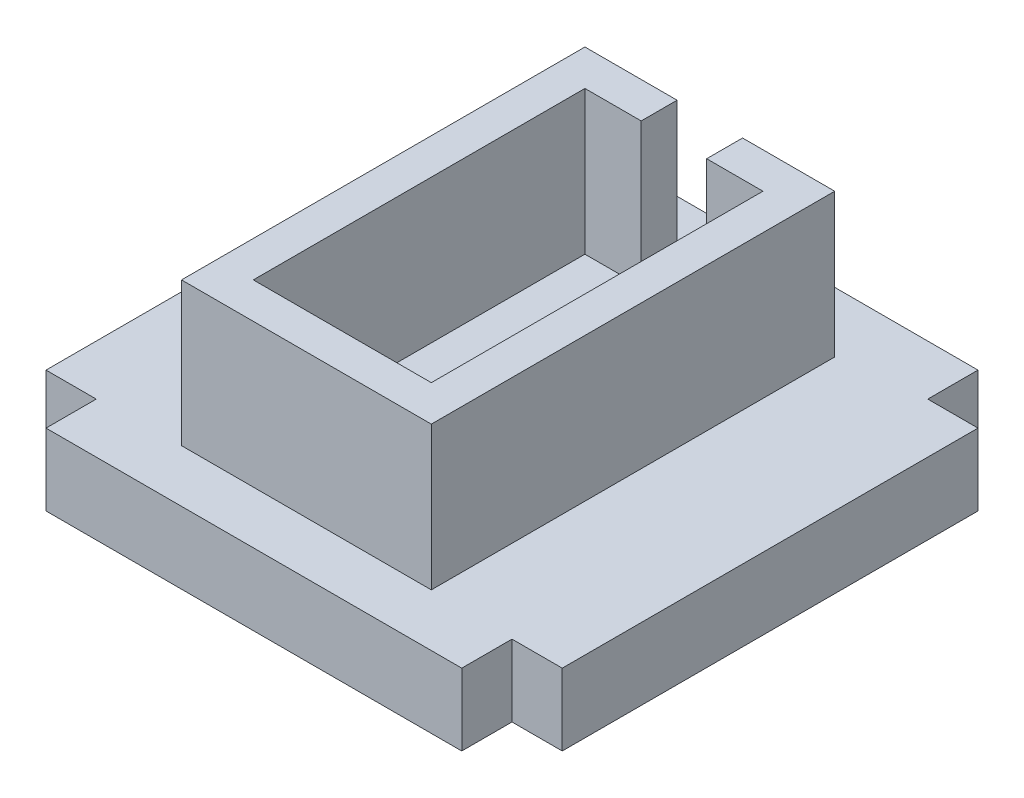
SolidWorks part; units mm, degrees
ref_plane "Front Plane" through (0, 0, 0) normal (0, 0, 1) x (1, 0, 0)
ref_plane "Top Plane" through (0, 0, 0) normal (0, 1, 0) x (1, 0, 0)
ref_plane "Right Plane" through (0, 0, 0) normal (1, 0, 0) x (0, 0, -1)
sketch "Sketch21" plane through (0, 0, 0) normal (0, 1, 0) x (1, 0, 0)
  line L22 (0, 17.98) -> (-14.48, 17.98)
  line L23 (-14.48, 17.98) -> (-14.48, 14.48)
  line L24 (-14.48, 14.48) -> (-17.98, 14.48)
  line L25 (-17.98, -14.48) -> (-14.48, -14.48)
  line L26 (-14.48, -14.48) -> (-14.48, -17.98)
  line L27 (-14.48, -17.98) -> (0, -17.98)
  line L28 (0, -17.98) -> (14.48, -17.98)
  line L29 (14.48, -17.98) -> (14.48, -14.48)
  line L30 (14.48, -14.48) -> (17.98, -14.48)
  line L31 (17.98, 14.48) -> (14.48, 14.48)
  line L32 (14.48, 14.48) -> (14.48, 17.98)
  line L33 (14.48, 17.98) -> (0, 17.98)
  line L34 (-17.98, 0) -> (-17.98, 14.48)
  line L35 (-17.98, -14.48) -> (-17.98, 0)
  line L36 (17.98, 0) -> (17.98, 14.48)
  line L37 (17.98, 0) -> (17.98, -14.48)
  dimension "D1" = 3.5
  dimension "D2" = 14.48
  dimension "D3" = 14.48
  dimension "D4" = 35.96
  dimension "D5" = 35.96
  dimension "D13" = 14.48
extrude "Boss-Extrude18" add sketch "Sketch21" along normal blind 5
sketch "Sketch23" plane through (0, 5, 0) normal (0, 1, 0) x (1, 0, 0)
  line L0 (-8.7, 13.78) -> (-2.28, 13.78)
  line L2 (-8.7, 13.78) -> (-8.7, -14.32)
  line L3 (-8.7, -14.32) -> (8.7, -14.32)
  line L4 (8.7, 13.78) -> (8.7, -14.32)
  line L5 (-2.28, 13.78) -> (-2.28, 11.28)
  line L6 (-2.28, 11.28) -> (-6.2, 11.28)
  line L7 (-6.2, 11.28) -> (-6.2, -11.82)
  line L8 (-6.2, -11.82) -> (6.2, -11.82)
  line L9 (6.2, -11.82) -> (6.2, 11.28)
  line L10 (6.2, 11.28) -> (2.28, 11.28)
  line L11 (2.28, 11.28) -> (2.28, 13.78)
  line L12 (2.28, 13.78) -> (8.7, 13.78)
  line L16 (14.48, 17.98) -> (-14.48, 17.98) construction
  point P0 (0, 0)
  dimension "D1" = 6.2
  dimension "D2" = 12.4
  dimension "D3" = 4.2
  dimension "D4" = 23.1
  dimension "D5" = 2.5
  dimension "D6" = 2.5
  dimension "D7" = 2.5
  dimension "D8" = 2.5
  dimension "D9" = 3.92
  dimension "D10" = 3.92
extrude "Boss-Extrude19" add sketch "Sketch23" along normal blind 10
